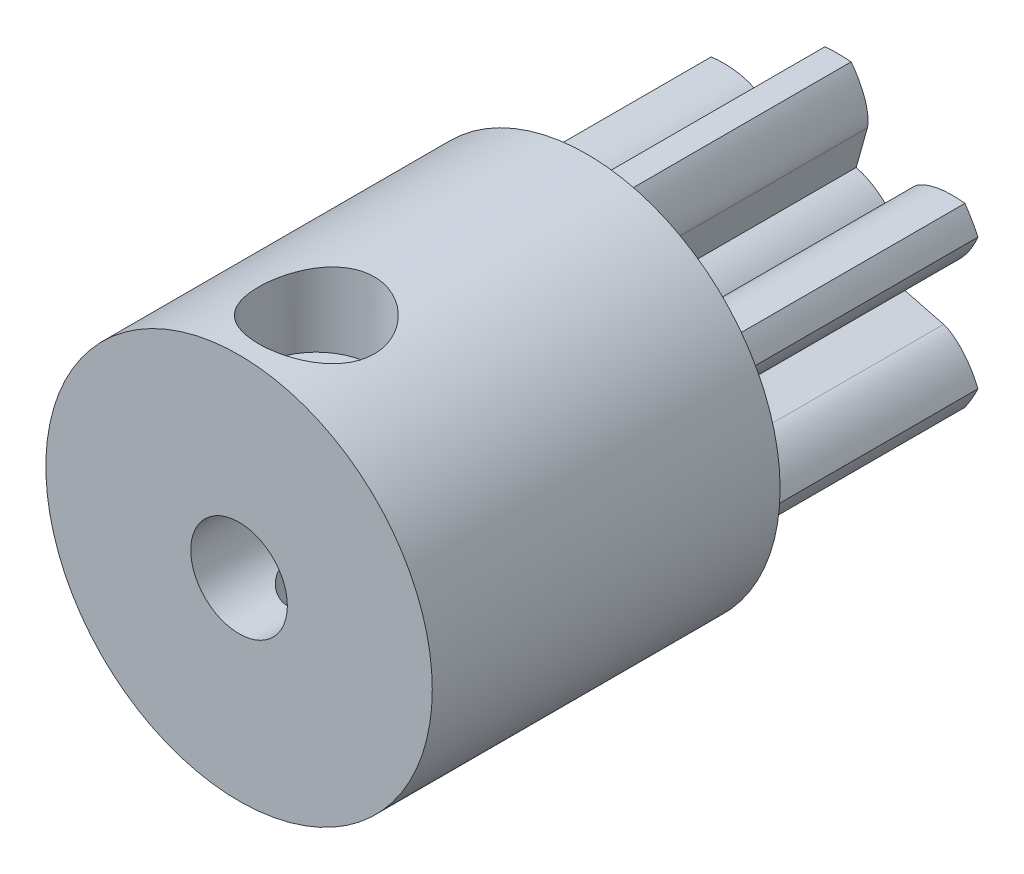
SolidWorks part; units mm, degrees
ref_plane "前视基准面" through (0, 0, 0) normal (0, 0, 1) x (1, 0, 0)
ref_plane "上视基准面" through (0, 0, 0) normal (0, 1, 0) x (1, 0, 0)
ref_plane "右视基准面" through (0, 0, 0) normal (1, 0, 0) x (0, 0, -1)
other "Configuration Table"
sketch "草图1" plane through (0, 0, 0) normal (0, 0, 1) x (1, 0, 0)
  line L0 (0, 0) -> (3, 0) construction
  line L1 (0, 0) -> (2.8978, 0.7765) construction
  line L2 (0, 0) -> (2.7305, 0.701)
  line L3 (2.8978, 0.7765) -> (2.8978, -0.7765) construction
  line L4 (0, 0) -> (2.7305, -0.701)
  circle A0 centre (0, 0) radius 4
  circle A1 centre (0, 0) radius 3 construction
  circle A2 centre (0, 0) radius 1.75
  circle A3 centre (0, 0) radius 2.8191 construction
  circle A4 centre (0, 0) radius 1.25
  spline S0 degree 4 poles (2.7305, 0.701) (2.7514, 0.7063) (2.8083, 0.7255) (2.9105, 0.779) (3.0627, 0.8875) (3.236, 1.0573) (3.4253, 1.3046) (3.6012, 1.6247) (3.742, 2.0003) (3.8364, 2.4221) (3.8779, 2.852) (3.8707, 3.2837) (3.8157, 3.7334) (3.69, 4.2802) (3.4574, 4.9086) (3.0836, 5.5918) (2.5556, 6.2772) (1.9356, 6.8796) (1.2391, 7.3923) (0.4849, 7.8122) (-0.3175, 8.1368) (-1.1468, 8.3674) (-2.0054, 8.5023) (-2.7502, 8.5427) (-3.4127, 8.5171) (-3.8849, 8.4708) (-4.3024, 8.4076) (-4.5772, 8.3558) (-4.9624, 8.2714) (-5.2496, 8.1908) (-5.5362, 8.1071) (-5.6783, 8.056) (-5.7704, 8.0254) knots 0 0 0 0 0 0.005604 0.015718 0.02996 0.048734 0.068727 0.096889 0.125051 0.153212 0.181374 0.209535 0.237696 0.271429 0.327752 0.384075 0.440398 0.496721 0.553044 0.609367 0.66569 0.722013 0.778336 0.834659 0.86282 0.890982 0.909091 0.931818 0.954545 0.977273 1 1 1 1 1 construction
  spline S1 degree 4 poles (2.7305, 0.701) (2.7514, 0.7063) (2.8083, 0.7255) (2.9105, 0.779) (3.0627, 0.8875) (3.236, 1.0573) (3.4253, 1.3046) (3.6012, 1.6247) (3.742, 2.0003) (3.8364, 2.4221) (3.8779, 2.852) (3.8707, 3.2837) (3.8157, 3.7334) (3.69, 4.2802) (3.4574, 4.9086) (3.0836, 5.5918) (2.5556, 6.2772) (1.9356, 6.8796) (1.2391, 7.3923) (0.4849, 7.8122) (-0.3175, 8.1368) (-1.1468, 8.3674) (-2.0054, 8.5023) (-2.7502, 8.5427) (-3.4127, 8.5171) (-3.8849, 8.4708) (-4.2047, 8.4224) (-4.3632, 8.395) (-4.4251, 8.3835) knots 0 0 0 0 0 0.005604 0.015718 0.02996 0.048734 0.068727 0.096889 0.125051 0.153212 0.181374 0.209535 0.237696 0.271429 0.327752 0.384075 0.440398 0.496721 0.553044 0.609367 0.66569 0.722013 0.778336 0.834659 0.86282 0.890982 0.909091 0.909091 0.909091 0.909091 0.909091
  spline S2 degree 4 poles (2.7305, -0.701) (2.7514, -0.7063) (2.8083, -0.7255) (2.9105, -0.779) (3.0627, -0.8875) (3.236, -1.0573) (3.4253, -1.3046) (3.6012, -1.6247) (3.742, -2.0003) (3.8364, -2.4221) (3.8779, -2.852) (3.8707, -3.2837) (3.8157, -3.7334) (3.69, -4.2802) (3.4574, -4.9086) (3.0836, -5.5918) (2.5556, -6.2772) (1.9356, -6.8796) (1.2391, -7.3923) (0.4849, -7.8122) (-0.3175, -8.1368) (-1.1468, -8.3674) (-2.0054, -8.5023) (-2.7502, -8.5427) (-3.4127, -8.5171) (-3.8849, -8.4708) (-4.3024, -8.4076) (-4.5772, -8.3558) (-4.9624, -8.2714) (-5.2496, -8.1908) (-5.5362, -8.1071) (-5.6783, -8.056) (-5.7704, -8.0254) knots 0 0 0 0 0 0.005604 0.015718 0.02996 0.048734 0.068727 0.096889 0.125051 0.153212 0.181374 0.209535 0.237696 0.271429 0.327752 0.384075 0.440398 0.496721 0.553044 0.609367 0.66569 0.722013 0.778336 0.834659 0.86282 0.890982 0.909091 0.931818 0.954545 0.977273 1 1 1 1 1 construction
  spline S3 degree 4 poles (2.7305, -0.701) (2.7514, -0.7063) (2.8083, -0.7255) (2.9105, -0.779) (3.0627, -0.8875) (3.236, -1.0573) (3.4253, -1.3046) (3.6012, -1.6247) (3.742, -2.0003) (3.8364, -2.4221) (3.8779, -2.852) (3.8707, -3.2837) (3.8157, -3.7334) (3.69, -4.2802) (3.4574, -4.9086) (3.0836, -5.5918) (2.5556, -6.2772) (1.9356, -6.8796) (1.2391, -7.3923) (0.4849, -7.8122) (-0.3175, -8.1368) (-1.1468, -8.3674) (-2.0054, -8.5023) (-2.7502, -8.5427) (-3.4127, -8.5171) (-3.8849, -8.4708) (-4.2047, -8.4224) (-4.3632, -8.395) (-4.4251, -8.3835) knots 0 0 0 0 0 0.005604 0.015718 0.02996 0.048734 0.068727 0.096889 0.125051 0.153212 0.181374 0.209535 0.237696 0.271429 0.327752 0.384075 0.440398 0.496721 0.553044 0.609367 0.66569 0.722013 0.778336 0.834659 0.86282 0.890982 0.909091 0.909091 0.909091 0.909091 0.909091
  point P15 (2.8978, 0)
  dimension "齿顶圆直径" = 8
  dimension "分度圆直径" = 6
  dimension "齿根圆直径" = 3.5
  dimension "基圆直径" = 5.6382
  dimension "内孔直径" = 2.5
  dimension "渐近线镜像线夹角" = 15
extrude "凸台-拉伸1" add sketch "草图1" along normal blind 6.5 contours A0 | A4
extrude "切除-拉伸1" cut sketch "草图1<3>" along normal through all contours A2 S3 A0 S1 region at (3.0753, 0, 0)
sketch "草图1<3>" plane through (0, 0, 0) normal (0, 0, 1) x (1, 0, 0) same geometry as "草图1"
pattern_circular "阵列(圆周)1" count 6 every 60 about axis through (0, 0, 6.5) along (0, 0, 1) of "切除-拉伸1"
sketch "草图2" plane through (0, 0, 6.5) normal (0, 0, 1) x (1, 0, 0)
  circle A0 centre (0, 0) radius 1.25
  circle A1 centre (0, 0) radius 5
  circle A2 centre (0, 0) radius 1.25 construction
  dimension "D1" = 10
extrude "凸台-拉伸2" add sketch "草图2" along normal blind 9 contours A1 | A0
extrude "凸台-拉伸3" add sketch "草图2<4>" against normal up to surface (6.5 mm away) contours A0 up to face at (0, 0, 0)
sketch "草图2<4>" plane through (0, 0, 6.5) normal (0, 0, 1) x (1, 0, 0) same geometry as "草图2"
sketch "草图3" plane through (0, 0, 0) normal (0, 1, 0) x (1, 0, 0)
  circle A0 centre (0, -13.5) radius 1.5
  circle A1 centre (0, -13.5) radius 0.75
  dimension "D1" = 1.5
  dimension "D2" = 3
  dimension "D3" = 13.5
extrude "切除-拉伸2" cut sketch "草图3" against normal through all both and the other way through all contours A1
extrude "切除-拉伸3" cut sketch "草图3<5>" against normal blind 2 from offset 5 contours A0
sketch "草图3<5>" plane through (0, 0, 0) normal (0, 1, 0) x (1, 0, 0) same geometry as "草图3"
equation "\"m\"= 1'模数"
equation "\"z\"= 6'齿数"
equation "\"a\"= 20度'压力角"
equation "\"d\"= \"m\" * \"z\"'分度圆直径"
equation "\"da\"= ( \"z\" + 2 ) * \"m\"'齿顶圆直径"
equation "\"df\"= ( \"z\" - 2.5 ) * \"m\"'齿根圆直径"
equation "\"s\"= 0.5 * PI * \"m\"'分度圆齿厚"
equation "\"r\"= 0.38 * \"m\"'齿根圆角"
equation "\"B\"= 0.3 * \"d\"'齿厚"
equation "\"db\"= \"m\" * \"z\" * cos ( \"a\" )'基圆直径"
equation "\"rb\"= \"db\" / 2'基圆半径"
equation "\"齿顶圆直径@草图1\"= \"da\""
equation "\"分度圆直径@草图1\"= \"d\""
equation "\"齿根圆直径@草图1\"= \"df\""
equation "\"基圆直径@草图1\"= \"db\""
equation "\"渐近线镜像线夹角@草图1\"= 360 / 4 / \"z\""
equation "\"h\"= 6.5'齿轮厚度"
equation "\"ir\"= 2.5'内孔直径"
equation "\"内孔直径@草图1\"= \"ir\""
equation "\"齿轮厚@凸台-拉伸1\"= \"h\""
equation "\"齿轮夹角@阵列(圆周)1\"= 360 / \"z\""
equation "\"齿数@阵列(圆周)1\"= \"z\""
